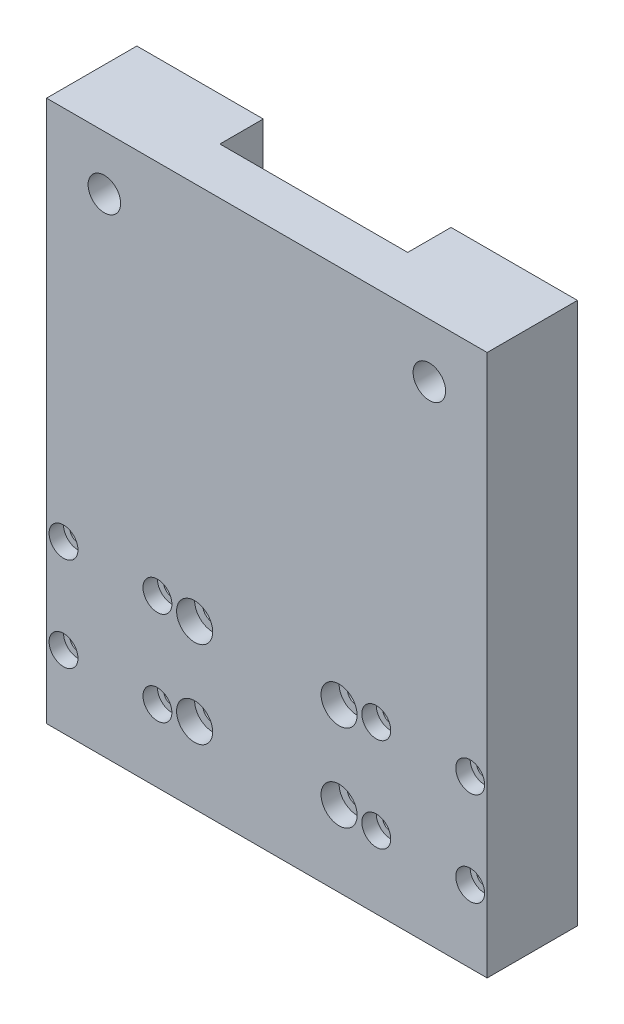
SolidWorks part; units mm, degrees
ref_plane "Front Plane" through (0, 0, 0) normal (0, 0, 1) x (1, 0, 0)
ref_plane "Top Plane" through (0, 0, 0) normal (0, 1, 0) x (1, 0, 0)
ref_plane "Right Plane" through (0, 0, 0) normal (1, 0, 0) x (0, 0, -1)
sketch "Sketch1" plane through (0, 0, 0) normal (0, 0, 1) x (1, 0, 0)
  line L1 (0, 0) -> (122, 0)
  line L2 (0, 0) -> (0, 150)
  line L3 (0, 150) -> (122, 150)
  line L4 (122, 0) -> (122, 150)
  dimension "D1" = 122
  dimension "D2" = 150
extrude "Boss-Extrude1" add sketch "Sketch1" along normal blind 25
sketch "Sketch2" plane through (0, 0, 25) normal (0, 0, 1) x (1, 0, 0)
  line L0 (61, 150) -> (61, 0) construction
  line L1 (122, 150) -> (0, 150) construction
  line L2 (0, 0) -> (122, 0) construction
  line L3 (0, 33) -> (122, 33) construction
  line L4 (0, 150) -> (0, 0) construction
  line L5 (122, 0) -> (122, 150) construction
  point P6 (30.7, 20)
  point P7 (30.7, 46)
  point P8 (4.7, 20)
  point P9 (4.7, 46)
  point P10 (117.3, 46)
  point P11 (117.3, 20)
  point P12 (91.3, 46)
  point P13 (91.3, 20)
  point P20 (41, 45)
  point P21 (81, 45)
  point P22 (81, 21)
  point P23 (41, 21)
  dimension "D1" = 30.3
  dimension "D2" = 26
  dimension "D3" = 26
  dimension "D4" = 20
  dimension "D5" = 13
  dimension "D6" = 12
  dimension "D7" = 20
hole_wizard "CBORE for M4 SHCS1" positions "3DSketch1" profile "Sketch3" counterbore size "M4" standard "ANSI Metric" end condition through all
sketch3d "3DSketch1"
  point P0 (4.7, 46, 25)
  point P3 (30.7, 46, 25)
  point P6 (4.7, 20, 25)
  point P9 (30.7, 20, 25)
  point P12 (91.3, 46, 25)
  point P15 (117.3, 46, 25)
  point P18 (117.3, 20, 25)
  point P21 (91.3, 20, 25)
sketch "Sketch3" plane through (4.7, 46, 25) normal (1, 0, 0) x (0, -1, 0)
  line L0 (0, 0) -> (0, 25)
  line L1 (0, 25) -> (2.25, 25)
  line L3 (2.25, 25) -> (2.25, 4)
  line L4 (2.25, 4) -> (4, 4)
  line L5 (4, 4) -> (4, 0)
  line L7 (4, 0) -> (0, 0)
  line L11 (0, -6.35) -> (0, 107.95) construction
  dimension "Thru Hole Dia." = 4.5
  dimension "Thru Hole Depth" = 25
  dimension "C'Bore Dia." = 8
  dimension "C'Bore Depth" = 4
sketch "Sketch4" plane through (0, 0, 0) normal (0, 1, 0) x (1, 0, 0)
  line L0 (61, 0) -> (61, -20.062) construction
  line L1 (122, 0) -> (0, 0) construction
  line L2 (35, 0) -> (35, -12)
  line L3 (35, -12) -> (87, -12)
  line L4 (87, 0) -> (87, -12)
  line L5 (35, 0) -> (87, 0)
  point P8 (61, -12)
  dimension "D1" = 26
  dimension "D2" = 12
extrude "Cut-Extrude1" cut sketch "Sketch4" along normal through all
hole_wizard "CBORE for M5 SHCS1" positions "3DSketch3" profile "Sketch7" counterbore size "M5" standard "ANSI Metric" end condition through all
sketch3d "3DSketch3"
  point P0 (41, 45, 25)
  point P3 (81, 45, 25)
  point P6 (81, 21, 25)
  point P9 (41, 21, 25)
sketch "Sketch7" plane through (41, 45, 25) normal (1, 0, 0) x (0, -1, 0)
  line L0 (0, 0) -> (0, 25)
  line L1 (0, 25) -> (2.75, 25)
  line L3 (2.75, 25) -> (2.75, 5)
  line L4 (2.75, 5) -> (5, 5)
  line L5 (5, 5) -> (5, 0)
  line L7 (5, 0) -> (0, 0)
  line L11 (0, -6.35) -> (0, 107.95) construction
  dimension "Thru Hole Dia." = 5.5
  dimension "Thru Hole Depth" = 25
  dimension "C'Bore Dia." = 10
  dimension "C'Bore Depth" = 5
sketch "Sketch8" plane through (0, 0, 0) normal (0, 0, -1) x (-1, 0, 0)
  line L0 (-87, 135) -> (-35, 135) construction
  line L1 (-87, 0) -> (-87, 150) construction
  line L2 (-35, 0) -> (-35, 150) construction
  line L3 (-35, 150) -> (-87, 150) construction
  line L4 (-61, 150) -> (-61, 0) construction
  line L5 (-61, 150) -> (-61, 122.8733) construction
  point P8 (-106, 135)
  point P14 (-16, 135)
  dimension "D1" = 15
  dimension "D2" = 45
hole_wizard "CBORE for M8 SHCS1" positions "3DSketch5" profile "Sketch10" counterbore size "M8" standard "ANSI Metric" end condition through all
sketch3d "3DSketch5"
  point P0 (106, 135, 0)
  point P3 (16, 135, 0)
sketch "Sketch10" plane through (106, 135, 0) normal (1, 0, 0) x (0, 1, 0)
  line L0 (0, 0) -> (0, 25)
  line L1 (0, 25) -> (4.5, 25)
  line L3 (4.5, 25) -> (4.5, 8)
  line L4 (4.5, 8) -> (7.5, 8)
  line L5 (7.5, 8) -> (7.5, 0)
  line L7 (7.5, 0) -> (0, 0)
  line L11 (0, -6.35) -> (0, 107.95) construction
  dimension "Thru Hole Dia." = 9
  dimension "Thru Hole Depth" = 25
  dimension "C'Bore Dia." = 15
  dimension "C'Bore Depth" = 8
